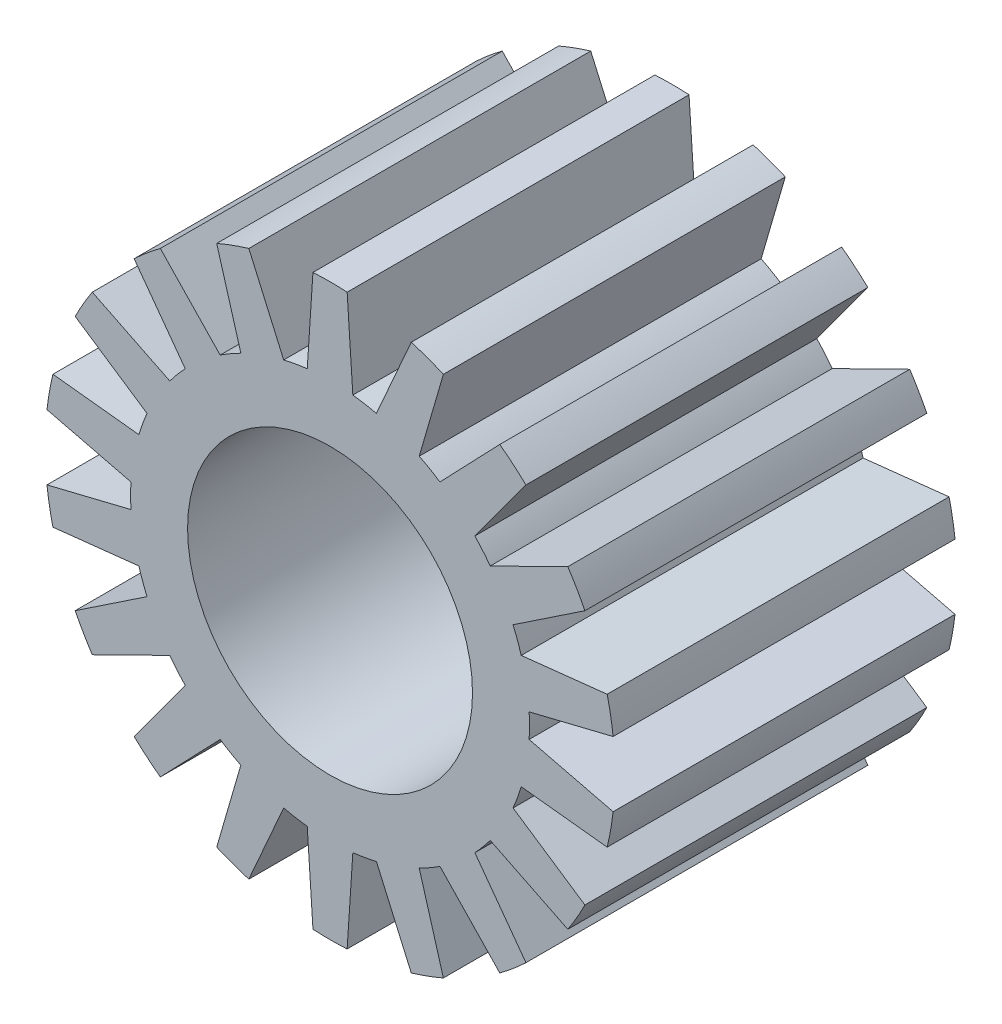
SolidWorks part; units mm, degrees
ref_plane "Plano frontal" through (0, 0, 0) normal (0, 0, 1) x (1, 0, 0)
ref_plane "Plano superior" through (0, 0, 0) normal (0, 1, 0) x (1, 0, 0)
ref_plane "Plano direito" through (0, 0, 0) normal (1, 0, 0) x (0, 0, -1)
sketch "Esboço1" plane through (0, 0, 0) normal (0, 0, 1) x (1, 0, 0)
  line L0 (0, 5) -> (0, 4) construction
  line L1 (-0.3, 4.991) -> (-0.3, 3.9887) construction
  line L2 (0.3, 4.991) -> (0.3, 3.9887) construction
  line L3 (-0.4, 4.984) -> (-0.4, 3.4771) construction
  line L4 (0.4, 4.984) -> (0.4, 3.4771) construction
  line L5 (-0.4, 5) -> (-0.4, 3.5183) construction
  line L6 (-0.3, 5) -> (-0.3, 3.5183) construction
  line L7 (0, 5) -> (0, 3.5183) construction
  line L8 (0.3, 5) -> (0.3, 3.5183) construction
  line L9 (0.4, 5) -> (0.4, 3.5183) construction
  line L10 (-0.3, 4.991) -> (-0.4, 3.4771)
  line L11 (0.3, 4.991) -> (0.4, 3.4771)
  arc A0 (0.3, 4.991) -> (-0.3, 4.991) centre (0, 0) ccw
  circle A1 centre (0, 0) radius 2.5
  circle A2 centre (0, 0) radius 3.5
  point P38 (0, 0)
  dimension "D1" = 5
  dimension "D2" = 10
  dimension "D3" = 7
  dimension "D8" = 5
  dimension "D4" = 0.3
  dimension "D5" = 0.3
  dimension "D6" = 0.4
  dimension "D7" = 0.4
extrude "Ressalto-extrusão1" add sketch "Esboço1" along normal blind 6 contours A2 A1 region at (0, 3.401, 0)
extrude "Ressalto-extrusão2" add sketch "Esboço1<3>" along normal up to surface (6 mm away) contours A2 L11 A0 L10 region at (0, 4.209, 0) up to face at (2.5, 0, 6)
sketch "Esboço1<3>" plane through (0, 0, 0) normal (0, 0, 1) x (1, 0, 0) same geometry as "Esboço1"
pattern_circular "PadrãoCircular1" count 18 over 360 about axis through (0, 0, 6) along (0, 0, -1) of "Ressalto-extrusão2"
